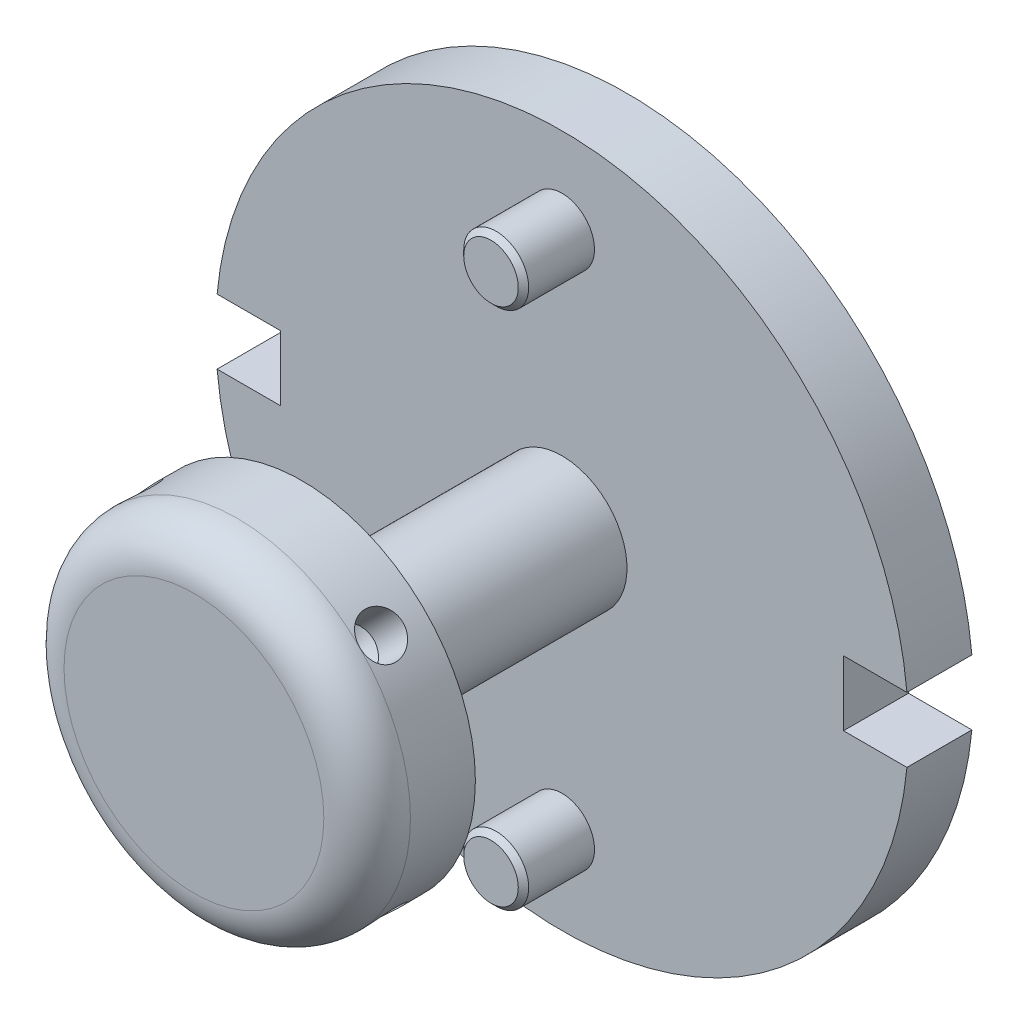
SolidWorks part; units mm, degrees
ref_plane "Front Plane" through (0, 0, 0) normal (0, 0, 1) x (1, 0, 0)
ref_plane "Top Plane" through (0, 0, 0) normal (0, 1, 0) x (1, 0, 0)
ref_plane "Right Plane" through (0, 0, 0) normal (1, 0, 0) x (0, 0, -1)
sketch "Sketch1" plane through (0, 0, 0) normal (0, 0, 1) x (1, 0, 0)
  line L1 (0, 0) -> (82.55, 0) construction
  line L6 (82.55, 60.1343) -> (82.55, -59.2289) construction
  line L7 (82.55, -9.525) -> (101.6, -9.525)
  line L8 (82.55, 9.525) -> (101.6, 9.525)
  line L9 (82.55, 9.525) -> (82.55, -9.525)
  line L11 (101.6, 9.525) -> (101.6, -9.525)
  line L12 (-82.55, 9.525) -> (-101.6, 9.525)
  line L13 (-82.55, 9.525) -> (-82.55, -9.525)
  line L14 (-82.55, -9.525) -> (-101.6, -9.525)
  line L15 (-101.6, 9.525) -> (-101.6, -9.525)
  circle A0 centre (0, 0) radius 101.6
  dimension "D1" = 101.6
  dimension "D2" = 82.55
  dimension "D3" = 9.525
extrude "Boss-Extrude1" add sketch "Sketch1" along normal blind 19.05 contours A0 L7 L9 L8 L12 L13 L14 region at (0, 0, 0)
ref_plane "Plane1" through (0, 0, 19.05) normal (0, 0, 1) x (1, 0, 0)
sketch "Sketch2" plane through (0, 0, 19.05) normal (0, 0, 1) x (1, 0, 0)
  line L0 (82.55, 0) -> (-82.55, 0) construction
  line L1 (82.55, 9.525) -> (82.55, -9.525) construction
  line L2 (-82.55, 9.525) -> (-82.55, -9.525) construction
  circle A1 centre (0, -76.2) radius 9.525
  circle A2 centre (0, 76.2) radius 9.525
  arc A3 (101.1525, 9.525) -> (-101.1525, 9.525) centre (0, 0) ccw construction
  dimension "D1" = 19.05
  dimension "D2" = 82.55
  dimension "D3" = 76.2
extrude "Boss-Extrude2" add sketch "Sketch2" along normal blind 20.828
chamfer "Chamfer1" distance 1.524 angle 45 2 edges at (9.525, -76.2, 39.878) (-9.525, 76.2, 39.878)
sketch "Sketch3" plane through (0, 0, 19.05) normal (0, 0, 1) x (1, 0, 0)
  circle A0 centre (0, 0) radius 19.05
  dimension "D1" = 38.1
extrude "Boss-Extrude3" add sketch "Sketch3" along normal blind 76.2 contours A0
ref_plane "Plane2" through (0, 0, 0) normal (0, 0, -1) x (-1, 0, 0)
sketch "Sketch4" plane through (0, 0, 0) normal (0, 0, -1) x (-1, 0, 0)
  circle A0 centre (0, 0) radius 25.4
  dimension "D1" = 50.8
extrude "Boss-Extrude4" add sketch "Sketch4" along normal blind 19.05 contours A0
ref_plane "Plane3" through (0, 0, -19.05) normal (0, 0, -1) x (-1, 0, 0)
sketch "Sketch5" plane through (0, 0, -19.05) normal (0, 0, -1) x (-1, 0, 0)
  circle A0 centre (0, 0) radius 19.05
  dimension "D1" = 38.1
extrude "Boss-Extrude5" add sketch "Sketch5" along normal blind 25.4 contours A0
ref_plane "Plane4" through (0, 0, 95.25) normal (0, 0, 1) x (1, 0, 0)
sketch "Sketch7" plane through (0, 0, 95.25) normal (0, 0, 1) x (1, 0, 0)
  circle A0 centre (0, 0) radius 50.8
  dimension "D1" = 101.6
extrude "Boss-Extrude6" add sketch "Sketch7" along normal blind 31.75 contours A0
ref_plane "Plane5" through (0, 0, 127) normal (0, 0, 1) x (1, 0, 0)
ref_plane "Plane7" through (35.921, 35.921, 0) normal (0.7071, 0.7071, 0) x (0, 0, -1)
hole_wizard "#92 (0.5) Diameter Hole1" positions "Sketch21" profile "Sketch22" hole size "#92" standard "ANSI Inch"
sketch "Sketch21" plane through (35.921, 35.921, 0) normal (0.7071, 0.7071, 0) x (0, 0, -1)
  line L0 (-95.25, -50.8) -> (-95.25, 50.8) construction
  point P0 (-107.95, 0)
  dimension "D1" = 12.7
sketch "Sketch22" plane through (35.921, 35.921, 107.95) normal (0, 0, 1) x (-0.7071, 0.7071, 0)
  line L0 (0, 0) -> (0, 16.002)
  line L1 (0, 16.002) -> (6.35, 12.1865)
  line L2 (6.35, 12.1865) -> (6.35, 0)
  line L5 (6.35, 0) -> (0, 0)
  line L10 (0, 16.002) -> (-6.35, 12.1865) construction
  line L11 (0, -6.35) -> (0, 107.95) construction
  dimension "Hole Dia." = 12.7
  dimension "Hole Depth" = 16.002
  dimension "Drill Angle" = 118
pattern_circular "CirPattern2" count 4 over 360 about axis through (0, 0, 127) along (0, 0, -1) of "#92 (0.5) Diameter Hole1" reverse direction yes
fillet "Fillet2" radius 12.7 1 edges at (50.8, 0, 127)
